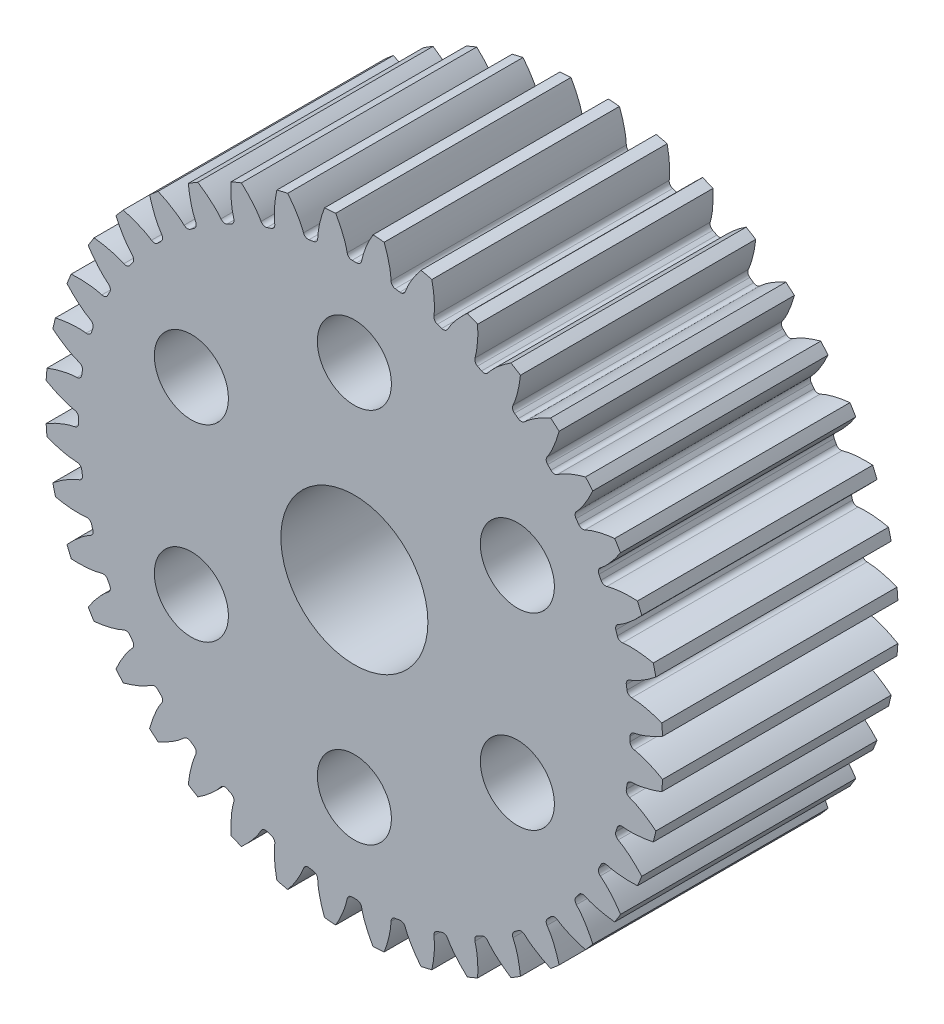
SolidWorks part; units mm, degrees
material "Plain Carbon Steel"
ref_plane "Front Plane" through (0, 0, 0) normal (0, 0, 1) x (1, 0, 0)
ref_plane "Top Plane" through (0, 0, 0) normal (0, 1, 0) x (1, 0, 0)
ref_plane "Right Plane" through (0, 0, 0) normal (1, 0, 0) x (0, 0, -1)
sketch "Sketch1" plane through (0, 0, 0) normal (0, 0, 1) x (1, 0, 0)
  line L0 (0, 0) -> (0, 15.875) construction
  line L1 (-5.1021, 17.732) -> (5.1021, 14.018) construction
  circle A0 centre (0, 0) radius 14.8828 construction
  circle A1 centre (0, 0) radius 16.6687 construction
  circle A2 centre (0, 0) radius 15.875 construction
  circle A3 centre (0, 0) radius 14.9176 construction
  point P8 (406.4, 0)
  point P13 (508, 0)
  dimension "OD | Outside Diameter" = 33.3375
  dimension "Root Diameter" = 29.7656
  dimension "Gear Pitch Diameter" = 31.75
  dimension "Base Diameter" = 29.8352
  dimension "Pressure Angle" = 20
  dimension "Number of Teeth" = 1016
  dimension "Gear Pitch | Diametral Pitch" = 812.8
sketch "Sketch2" plane through (0, 0, 0) normal (1, 0, 0) x (0, 0, -1)
  line L0 (-6.35, 0) -> (6.35, 0) construction
  point P2 (10.3187, 0)
  point P5 (18.6531, 0)
  point P6 (-10.3187, 0)
  dimension "Length" = 12.7
  dimension "D1" = 16.6687
  dimension "D2" = 25.0031
  dimension "D3" = 16.6687
sketch "Sketch3" plane through (0, 0, 0) normal (0, 0, 1) x (1, 0, 0)
  circle A0 centre (0, 0) radius 16.6687
  circle A1 centre (0, 0) radius 16.6687 construction
extrude "Boss-Extrude1" add sketch "Sketch3" against normal up to vertex (6.35 mm away) and the other way up to vertex (6.35 mm away) up to point (0, 0, -6.35) other way up to point (0, 0, 6.35)
sketch "Sketch4" plane through (0, 0, 0) normal (0, 0, 1) x (1, 0, 0)
  line L0 (0, 0) -> (14.8784, 0.3626) construction
  line L2 (0, 0) -> (14.8784, -0.3626) construction
  line L4 (14.8784, 0.3626) -> (14.9132, 0.3634)
  line L5 (14.9132, -0.3634) -> (14.8784, -0.3626)
  arc A0 (14.8784, 0.3626) -> (14.8784, -0.3626) centre (0, 0) cw
  arc A3 (16.6383, 1.0067) -> (16.6383, -1.0067) centre (0, 0) cw
  circle A4 centre (0, 0) radius 16.6687 construction
  spline S0 degree 4 poles (14.9132, 0.3634) (14.9159, 0.3635) (14.9236, 0.3639) (14.9381, 0.3649) (14.9618, 0.3671) (14.9919, 0.3706) (15.0308, 0.376) (15.0766, 0.3835) (15.1268, 0.3928) (15.1814, 0.4042) (15.2358, 0.4166) (15.29, 0.4301) (15.3439, 0.4444) (15.4091, 0.4628) (15.4872, 0.4863) (15.5783, 0.516) (15.6814, 0.5524) (15.7862, 0.5921) (15.8891, 0.6335) (15.9927, 0.678) (16.0929, 0.7228) (16.1965, 0.7721) (16.2921, 0.8189) (16.3988, 0.8743) (16.4848, 0.9199) (16.5978, 0.9832) (16.6645, 1.0215) (16.7423, 1.0675) (16.7768, 1.0885) (16.798, 1.1014) knots 0 0 0 0 0 0.005377 0.015084 0.028532 0.04661 0.064855 0.092111 0.119476 0.146842 0.174209 0.201575 0.228941 0.256307 0.307035 0.361767 0.4165 0.471232 0.525964 0.580697 0.635429 0.690161 0.744894 0.799626 0.854358 0.909091 0.954545 1 1 1 1 1 construction
  spline S1 degree 4 poles (14.9132, 0.3634) (14.9159, 0.3635) (14.9236, 0.3639) (14.9381, 0.3649) (14.9618, 0.3671) (14.9919, 0.3706) (15.0308, 0.376) (15.0766, 0.3835) (15.1268, 0.3928) (15.1814, 0.4042) (15.2358, 0.4166) (15.29, 0.4301) (15.3439, 0.4444) (15.4091, 0.4628) (15.4872, 0.4863) (15.5783, 0.516) (15.6814, 0.5524) (15.7862, 0.5921) (15.8891, 0.6335) (15.9927, 0.678) (16.0929, 0.7228) (16.1965, 0.7721) (16.2921, 0.8189) (16.3988, 0.8743) (16.4848, 0.9199) (16.5733, 0.9695) (16.6163, 0.994) (16.6383, 1.0067) knots 0 0 0 0 0 0.005377 0.015084 0.028532 0.04661 0.064855 0.092111 0.119476 0.146842 0.174209 0.201575 0.228941 0.256307 0.307035 0.361767 0.4165 0.471232 0.525964 0.580697 0.635429 0.690161 0.744894 0.799626 0.854358 0.909091 0.909091 0.909091 0.909091 0.909091
  spline S2 degree 4 poles (14.9132, -0.3634) (14.9159, -0.3635) (14.9236, -0.3639) (14.9381, -0.3649) (14.9618, -0.3671) (14.9919, -0.3706) (15.0308, -0.376) (15.0766, -0.3835) (15.1268, -0.3928) (15.1814, -0.4042) (15.2358, -0.4166) (15.29, -0.4301) (15.3439, -0.4444) (15.4091, -0.4628) (15.4872, -0.4863) (15.5783, -0.516) (15.6814, -0.5524) (15.7862, -0.5921) (15.8891, -0.6335) (15.9927, -0.678) (16.0929, -0.7228) (16.1965, -0.7721) (16.2921, -0.8189) (16.3988, -0.8743) (16.4848, -0.9199) (16.5978, -0.9832) (16.6645, -1.0215) (16.7423, -1.0675) (16.7768, -1.0885) (16.798, -1.1014) knots 0 0 0 0 0 0.005377 0.015084 0.028532 0.04661 0.064855 0.092111 0.119476 0.146842 0.174209 0.201575 0.228941 0.256307 0.307035 0.361767 0.4165 0.471232 0.525964 0.580697 0.635429 0.690161 0.744894 0.799626 0.854358 0.909091 0.954545 1 1 1 1 1 construction
  spline S3 degree 4 poles (14.9132, -0.3634) (14.9159, -0.3635) (14.9236, -0.3639) (14.9381, -0.3649) (14.9618, -0.3671) (14.9919, -0.3706) (15.0308, -0.376) (15.0766, -0.3835) (15.1268, -0.3928) (15.1814, -0.4042) (15.2358, -0.4166) (15.29, -0.4301) (15.3439, -0.4444) (15.4091, -0.4628) (15.4872, -0.4863) (15.5783, -0.516) (15.6814, -0.5524) (15.7862, -0.5921) (15.8891, -0.6335) (15.9927, -0.678) (16.0929, -0.7228) (16.1965, -0.7721) (16.2921, -0.8189) (16.3988, -0.8743) (16.4848, -0.9199) (16.5733, -0.9695) (16.6163, -0.994) (16.6383, -1.0067) knots 0 0 0 0 0 0.005377 0.015084 0.028532 0.04661 0.064855 0.092111 0.119476 0.146842 0.174209 0.201575 0.228941 0.256307 0.307035 0.361767 0.4165 0.471232 0.525964 0.580697 0.635429 0.690161 0.744894 0.799626 0.854358 0.909091 0.909091 0.909091 0.909091 0.909091
  dimension "D1" = 29.7656
extrude "Cut-Extrude1" cut sketch "Sketch4" against normal through all both and the other way through all
fillet "Fillet1" radius 0.2663 2 edges at (14.8784, -0.3626, 0) (14.8784, 0.3626, 0)
pattern_circular "CirPattern1" count 40 over 360 about axis through (0, 0, 6.35) along (0, 0, -1) of "Cut-Extrude1", "Fillet1"
sketch "Sketch5" plane through (0, 0, 6.35) normal (0, 0, 1) x (1, 0, 0)
  point P0 (0, 0)
hole_wizard "5/16 (0.3125) Dowel Hole1" positions "Sketch5" profile "Sketch6" hole size "5/16" standard "ANSI Inch" end condition through all
sketch "Sketch6" plane through (0, 0, 6.35) normal (1, 0, 0) x (0, -1, 0)
  line L0 (0, 0) -> (0, 12.7)
  line L1 (0, 12.7) -> (3.9687, 12.7)
  line L2 (3.9687, 12.7) -> (3.9687, 0)
  line L5 (3.9687, 0) -> (0, 0)
  line L11 (0, -6.35) -> (0, 107.95) construction
  dimension "Thru Hole Dia." = 7.9375
  dimension "Thru Hole Depth" = 12.7
sketch "Sketch7" plane through (0, 0, 6.35) normal (0, 0, 1) x (1, 0, 0)
  point P12 (0, 10.16)
  point P14 (0, 0)
hole_wizard "Ø4.0mm Dowel Hole1" positions "Sketch7" profile "Sketch8" hole size "Ø4.0" standard "ANSI Metric" end condition through all
sketch "Sketch8" plane through (0, 10.16, 6.35) normal (1, 0, 0) x (0, -1, 0)
  line L0 (0, 0) -> (0, 12.7)
  line L1 (0, 12.7) -> (2, 12.7)
  line L2 (2, 12.7) -> (2, 0)
  line L5 (2, 0) -> (0, 0)
  line L11 (0, -6.35) -> (0, 107.95) construction
  dimension "Thru Hole Dia." = 4
  dimension "Thru Hole Depth" = 12.7
sketch "Sketch9" plane through (0, 0, 0) normal (1, 0, 0) x (0, 0, -1)
  line L0 (-12.2853, 0) -> (10.6845, 0)
pattern_circular "CirPattern2" count 6 over 360 about axis through (0, 0, 12.2853) along (0, 0, -1) of "Ø4.0mm Dowel Hole1" reverse direction yes
equation "\"Root Diameter@Sketch1\"=\"Root Diameter\""
equation "\"OD | Outside Diameter@Sketch1\"=\"Outside Diameter\""
equation "\"D1@CirPattern1\"=\"Number of Teeth\""
equation "\"Diametral Pitch\"=32"
equation "\"Number of Teeth\"= 40"
equation "\"Pressure Angle\"=20"
equation "\"Pitch Diameter\"= \"Number of Teeth\" / \"Diametral Pitch\""
equation "\"Base Diameter\"= \"Pitch Diameter\" * cos ( \"Pressure Angle\" )"
equation "\"Outside Diameter\"= ( \"Number of Teeth\" + 2 ) / \"Diametral Pitch\""
equation "\"Dedendum\"= 1.25 / \"Diametral Pitch\""
equation "\"Root Diameter\"= \"Pitch Diameter\" - ( 2 * \"Dedendum\" )"
equation "\"Pitch Angle\"= 360deg / \"Number of Teeth\""
equation "\"Alpha\"= sqr ( \"Pitch Diameter\" ^ 2 - \"Base Diameter\" ^ 2 ) / \"Base Diameter\" * 180 / PI - \"Pressure Angle\""
equation "\"Beta\"= ( \"Pitch Angle\" / 4 - \"Alpha\" )"
equation "\"Phi\"= sqr ( ( \"Outside Diameter\" / 2 ) ^ 2 - ( \"Base Diameter\" / 2 ) ^ 2 ) / ( \"Base Diameter\" / 2 )"
equation "\"Addendum\"= 1 / \"Diametral Pitch\""
equation "\"WorkingDepth\"= 2 / \"Diametral Pitch\""
equation "\"WholeDepth\"= 2.25 / \"Diametral Pitch\""
equation "\"Clearance\"= 0.25 / \"Diametral Pitch\""
equation "\"ToothThickness\"= ( pi * 2 ) / \"Diametral Pitch\""
equation "\"CircularPitch\"= pi / \"Diametral Pitch\""
equation "\"Number of Teeth@Sketch1\"=\"Number of Teeth\""
equation "\"Gear Pitch | Diametral Pitch@Sketch1\"=\"Diametral Pitch\""
equation "\"Pressure Angle@Sketch1\"=\"Pressure Angle\""
equation "\"Gear Pitch Diameter@Sketch1\"=\"Pitch Diameter\""
equation "\"Base Diameter@Sketch1\"=\"Base Diameter\""
equation "\"Fillet\"= \"Clearance\" * cos ( \"Pressure Angle\" ) * tan ( ( 90 + \"Pressure Angle\" ) / 2 )"
equation "\"D1@Fillet1\"=\"Fillet\""
equation "\"D1@Sketch4\"=if( \"Base Diameter\">\"Root Diameter\",\"Root Diameter\",\"Base Diameter\"-.00001)"
equation "\"D1@Sketch2\"=\"OD | Outside Diameter@Sketch1\"*2*0.5*0.5"
equation "\"D2@Sketch2\"=\"D1@Sketch2\"*1.5"
equation "\"D3@Sketch2\"=\"D1@Sketch2\""
equation "\"Length\"= .5in"
equation "\"Length@Sketch2\"= \"Length\""
